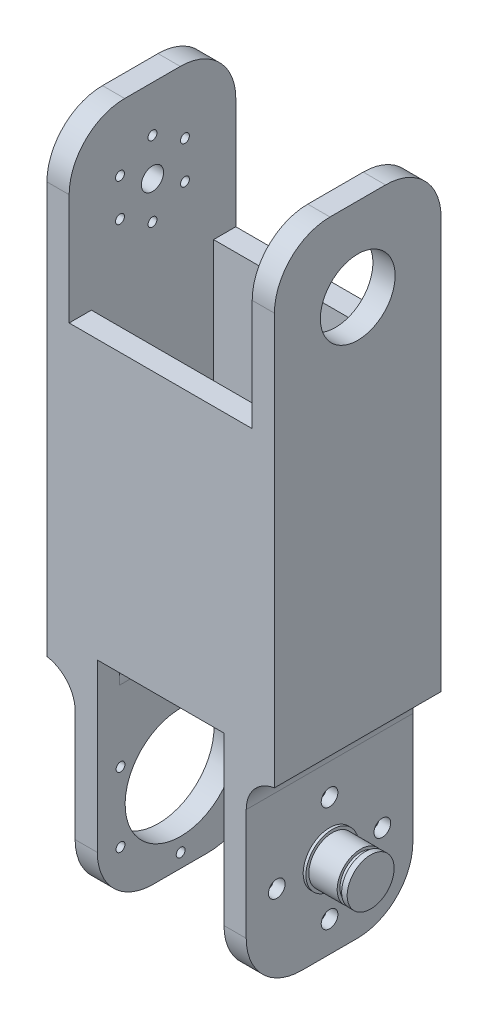
SolidWorks part; units mm, degrees
ref_plane "前视基准面" through (0, 0, 0) normal (0, 0, 1) x (1, 0, 0)
ref_plane "上视基准面" through (0, 0, 0) normal (0, 1, 0) x (1, 0, 0)
ref_plane "右视基准面" through (0, 0, 0) normal (1, 0, 0) x (0, 0, -1)
other "Configuration Table"
sketch "草图1" plane through (0, 0, 0) normal (1, 0, 0) x (0, 0, -1)
  line L1 (30, -80) -> (-30, -80)
  line L2 (30, -80) -> (30, 80)
  line L3 (30, 80) -> (-30, 80)
  line L4 (-30, -80) -> (-30, 80)
  line L5 (30, -80) -> (-30, 80) construction
  line L6 (30, 80) -> (-30, -80) construction
  point P0 (0, 0)
  dimension "D1" = 160
  dimension "D2" = 60
extrude "凸台-拉伸1" add sketch "草图1" along normal blind 8
sketch "草图2" plane through (8, 0, 0) normal (1, 0, 0) x (0, 0, -1)
  line L1 (30, 80) -> (-30, 80) construction
  circle A0 centre (0, 50) radius 13.5 construction
  circle A2 centre (0, 63.5) radius 1.6
  circle A4 centre (11.6913, 56.75) radius 1.6
  circle A5 centre (11.6913, 43.25) radius 1.6
  circle A6 centre (0, 36.5) radius 1.6
  circle A7 centre (-11.6913, 43.25) radius 1.6
  circle A8 centre (-11.6913, 56.75) radius 1.6
  circle A12 centre (0, 50) radius 4
  point P6 (0, 80)
  point P26 (0, 50)
  dimension "D3" = 27
  dimension "D7" = 3.2
  dimension "D11" = 8
  dimension "D2" = 30
  dimension "D9" = 6
extrude "切除-拉伸1" cut sketch "草图2" against normal through all
sketch "草图3" plane through (8, 0, 0) normal (1, 0, 0) x (0, 0, -1)
  line L0 (-30, 80) -> (-30, -80) construction
  line L1 (-22, -80) -> (-30, -80)
  line L2 (-22, -80) -> (-22, 20)
  line L3 (-22, 20) -> (-30, 20)
  line L4 (-30, -80) -> (-30, 20)
  line L5 (-22, -80) -> (-30, 20) construction
  line L6 (-22, 20) -> (-30, -80) construction
  line L7 (30, -80) -> (22, -80)
  line L8 (30, -80) -> (30, 20)
  line L9 (30, 20) -> (22, 20)
  line L10 (22, -80) -> (22, 20)
  line L11 (30, -80) -> (22, 20) construction
  line L12 (30, 20) -> (22, -80) construction
  line L13 (30, -80) -> (30, 80) construction
  line L14 (30, 80) -> (-30, 80) construction
  line L16 (-30, -80) -> (30, -80) construction
  point P0 (-26, -30)
  point P5 (26, -30)
  dimension "D1" = 60
  dimension "D3" = 60
  dimension "D5" = 8
  dimension "D6" = 8
extrude "凸台-拉伸2" add sketch "草图3" along normal blind 65.9
sketch "草图4" plane through (73.9, 0, 0) normal (1, 0, 0) x (0, 0, -1)
  line L0 (30, -80) -> (-30, 80) construction
  line L1 (30, -80) -> (-30, -80)
  line L2 (30, -80) -> (30, 80)
  line L3 (30, 80) -> (-30, 80)
  line L4 (-30, -80) -> (-30, 80)
  line L5 (30, -80) -> (-30, 80) construction
  line L6 (30, 80) -> (-30, -80) construction
  line L7 (30, 80) -> (-30, 80) construction
  point P0 (0, 0)
extrude "凸台-拉伸3" add sketch "草图4" along normal blind 8
sketch "草图9" plane through (73.9, 0, 0) normal (-1, 0, 0) x (0, 0, 1)
  circle A0 centre (0, 50) radius 13.45
  dimension "D1" = 26.9
extrude "切除-拉伸5" cut sketch "草图9" against normal up to next
sketch "草图11" plane through (0, 0, 30) normal (0, 0, 1) x (1, 0, 0)
  line L0 (0, 80) -> (0, -80) construction
  line L1 (0, -80) -> (18.15, -80)
  line L2 (0, -80) -> (0, -88)
  line L3 (0, -88) -> (18.15, -88)
  line L4 (18.15, -80) -> (18.15, -88)
  line L5 (81.9, -80) -> (63.75, -80)
  line L6 (81.9, -80) -> (81.9, -88)
  line L7 (81.9, -88) -> (63.75, -88)
  line L8 (63.75, -80) -> (63.75, -88)
  line L9 (81.9, 80) -> (81.9, -80) construction
  line L11 (18.15, -88) -> (10.15, -88)
  line L12 (18.15, -88) -> (18.15, -160)
  line L13 (18.15, -160) -> (10.15, -160)
  line L14 (10.15, -88) -> (10.15, -160)
  line L15 (63.75, -88) -> (71.75, -88)
  line L16 (63.75, -88) -> (63.75, -160)
  line L17 (63.75, -160) -> (71.75, -160)
  line L18 (71.75, -88) -> (71.75, -160)
  line M10 (0, -80) -> (81.9, -80)
  dimension "D1" = 8
  dimension "D2" = 8
  dimension "D3" = 45.6
  dimension "D4" = 72
  dimension "D5" = 72
  dimension "D6" = 8
  dimension "D7" = 8
extrude "凸台-拉伸4" add sketch "草图11" against normal blind 60 contours L3 L14 L13 L12 | L4 L2 L3 M10 | L8 L7 L6 M10 | L18 L7 L16 L17 region at (72.825, -84, 30) region at (9.075, -84, 30) region at (14.15, -124, 30) region at (67.75, -124, 30)
fillet "圆角1" radius 20 8 edges at (4, 80, -30) (4, 80, 30) (77.9, 80, -30) (77.9, 80, 30) (67.75, -160, -30) (67.75, -160, 30) (14.15, -160, -30) (14.15, -160, 30)
fillet "圆角2" radius 12 4 edges at (63.75, -80, 0) (18.15, -80, 0) (71.75, -88, 0) (10.15, -88, 0)
sketch "草图13" plane through (71.75, 0, 0) normal (1, 0, 0) x (0, 0, -1)
  line L0 (10, -160) -> (-10, -160) construction
  circle A0 centre (0, -130) radius 19 construction
  circle A1 centre (0, -111) radius 1.6
  circle A2 centre (19, -130) radius 1.6
  circle A3 centre (0, -149) radius 1.6
  circle A4 centre (-19, -130) radius 1.6
  point P4 (0, -160)
  point P5 (0.0241, -160.1066)
  point P17 (0, -130)
  dimension "D1" = 38
  dimension "D3" = 3.2
  dimension "D2" = 30
  dimension "D4" = 4
extrude "切除-拉伸6" cut sketch "草图13" against normal up to next
sketch "草图12" plane through (10.15, 0, 0) normal (-1, 0, 0) x (0, 0, 1)
  circle A0 centre (0, -130) radius 25 construction
  circle A1 centre (0, -105) radius 1.6
  circle A2 centre (21.6506, -117.5) radius 1.6
  circle A3 centre (21.6506, -142.5) radius 1.6
  circle A4 centre (0, -155) radius 1.6
  circle A5 centre (-21.6506, -142.5) radius 1.6
  circle A6 centre (-21.6506, -117.5) radius 1.6
  circle A7 centre (0, -130) radius 20
  point P17 (0, -130)
  dimension "D1" = 50
  dimension "D2" = 3.2
  dimension "D4" = 40
  dimension "D3" = 6
sketch "草图14" plane through (71.75, 0, 0) normal (1, 0, 0) x (0, 0, -1)
  circle A0 centre (0, -130) radius 8.45
  dimension "D1" = 16.9
extrude "凸台-拉伸5" add sketch "草图14" along normal blind 14.8
ref_plane "基准面1" through (84.55, 0, 0) normal (1, 0, 0) x (0, 0, -1)
sketch "草图15" plane through (84.55, 0, 0) normal (1, 0, 0) x (0, 0, -1)
  circle A0 centre (0, -130) radius 8.45
  circle A1 centre (0, -130) radius 7.45
  dimension "D1" = 16.9
  dimension "D2" = 14.9
extrude "切除-拉伸7" cut sketch "草图15" against normal blind 1.6
extrude "切除-拉伸8" cut sketch "草图12" against normal up to next
sketch "草图16" plane through (0, 0, 0) normal (-1, 0, 0) x (0, 0, 1)
  circle A0 centre (0, 63.5) radius 3
  circle A1 centre (11.6913, 56.75) radius 3
  circle A2 centre (11.6913, 43.25) radius 3
  circle A3 centre (0, 36.5) radius 3
  circle A4 centre (-11.6913, 43.25) radius 3
  circle A5 centre (-11.6913, 56.75) radius 3
  point P3 (0, 50)
  point P17 (0, 50)
  dimension "D1" = 6
  dimension "D2" = 6
extrude "切除-拉伸9" cut sketch "草图16" against normal blind 4
sketch "草图17" plane through (10.15, 0, 0) normal (-1, 0, 0) x (0, 0, 1)
  circle A0 centre (0, -105) radius 3
  circle A1 centre (21.6506, -117.5) radius 3
  circle A2 centre (21.6506, -142.5) radius 3
  circle A3 centre (0, -155) radius 3
  circle A4 centre (-21.6506, -142.5) radius 3
  circle A5 centre (-21.6506, -117.5) radius 3
  point P4 (0, -130)
  point P15 (0, -130)
  dimension "D1" = 6
  dimension "D2" = 6
extrude "切除-拉伸10" cut sketch "草图17" against normal blind 4
sketch "草图18" plane through (71.75, 0, 0) normal (1, 0, 0) x (0, 0, -1)
  circle A0 centre (0, -111) radius 3
  circle A1 centre (19, -130) radius 3
  circle A2 centre (0, -149) radius 3
  circle A3 centre (-19, -130) radius 3
  point P3 (0, -130)
  point P12 (0, -130)
  dimension "D1" = 6
  dimension "D2" = 4
extrude "切除-拉伸11" cut sketch "草图18" against normal blind 4
sketch "草图19" plane through (71.75, 0, 0) normal (1, 0, 0) x (0, 0, -1)
  circle A0 centre (0, -130) radius 9.5
  dimension "D1" = 19
extrude "凸台-拉伸6" add sketch "草图19" along normal blind 1
